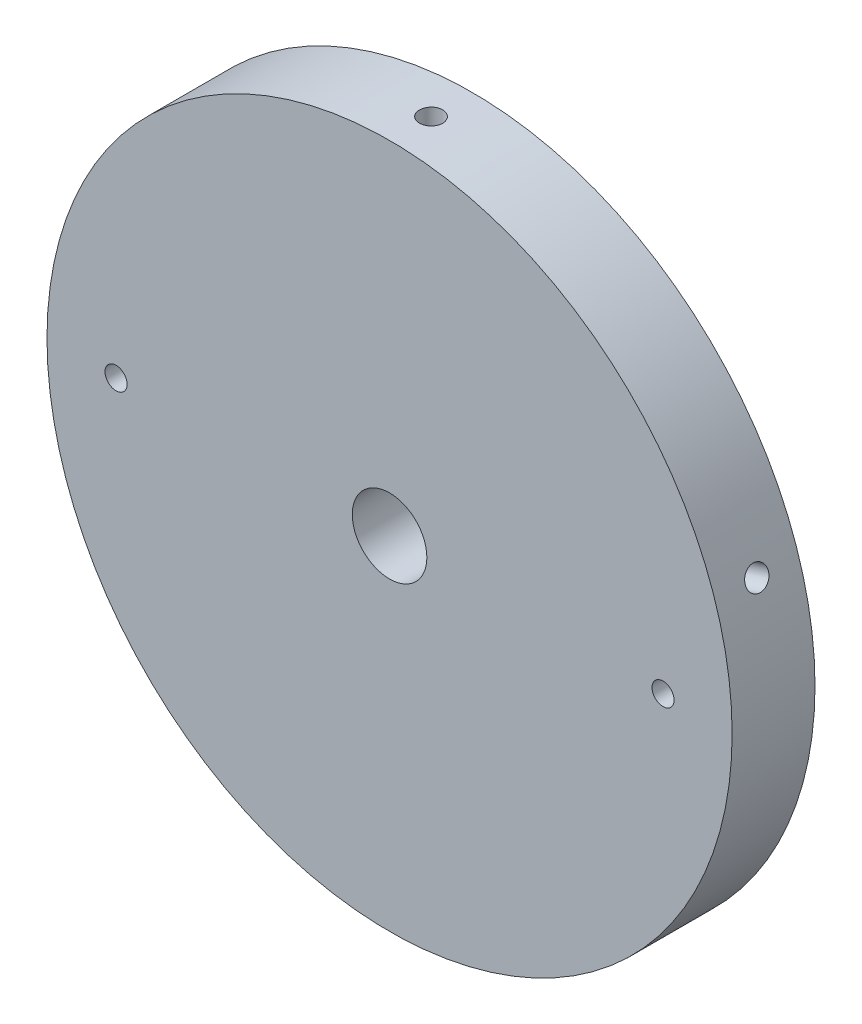
SolidWorks part; units mm, degrees
material "Polyetheretherketone (PEEK)"
ref_plane "Front Plane" through (0, 0, 0) normal (0, 0, 1) x (1, 0, 0)
ref_plane "Top Plane" through (0, 0, 0) normal (0, 1, 0) x (1, 0, 0)
ref_plane "Right Plane" through (0, 0, 0) normal (1, 0, 0) x (0, 0, -1)
sketch "Sketch1" plane through (0, 0, 0) normal (0, 0, 1) x (1, 0, 0)
  circle A0 centre (0, 0) radius 62
  dimension "D1" = 124
extrude "Boss-Extrude1" add sketch "Sketch1" along normal blind 15 contours A0
sketch "Sketch7" plane through (0, 0, 0) normal (0, 0, -1) x (-1, 0, 0)
  line L0 (0, 0) -> (-42.8683, 24.75) construction
  line L2 (0, 0) -> (-42.8683, -24.75) construction
  line L3 (-42.8683, -24.75) -> (-42.8683, 24.75) construction
  line L5 (0, 6.6) -> (0, -6.6) construction
  point P0 (-42.8683, 24.75)
  point P2 (-42.8683, -24.75)
  point P20 (42.8683, -24.75)
  point P21 (42.8683, 24.75)
  dimension "D1" = 49.5
  dimension "D2" = 49.5
sketch "Sketch9" plane through (0, 0, 0) normal (0, 0, -1) x (-1, 0, 0)
  point P0 (0, 0)
hole_wizard "M12 Clearance Hole1" positions "Sketch9" profile "Sketch10" hole size "M12" standard "ISO" end condition up to next
sketch "Sketch10" plane through (0, 0, 0) normal (1, 0, 0) x (0, 1, 0)
  line L0 (0, 0) -> (0, 15)
  line L1 (0, 15) -> (6.75, 15)
  line L2 (6.75, 15) -> (6.75, 0)
  line L5 (6.75, 0) -> (0, 0)
  line L11 (0, -6.35) -> (0, 107.95) construction
  dimension "Thru Hole Dia." = 13.5
  dimension "Thru Hole Depth" = 15
hole_wizard "M5 Tapped Hole1" positions "3DSketch1" profile "Sketch11" tap size "M5" standard "ISO"
sketch3d "3DSketch1"
  line L1 (0, 62, 7.5) -> (-58.9655, 19.1591, 7.5) construction
  line L2 (-58.9655, 19.1591, 7.5) -> (-36.4427, -50.1591, 7.5) construction
  line L3 (-36.4427, -50.1591, 7.5) -> (36.4427, -50.1591, 7.5) construction
  line L4 (36.4427, -50.1591, 7.5) -> (58.9655, 19.1591, 7.5) construction
  line L5 (58.9655, 19.1591, 7.5) -> (0, 62, 7.5) construction
  circle A0 centre (0, 0, 7.5) radius 62 construction
  circle A1 centre (0, 0, 0) radius 62 construction
  point P0 (0, 62, 7.5)
  point P2 (58.9655, 19.1591, 7.5)
  point P4 (36.4427, -50.1591, 7.5)
  point P6 (-36.4427, -50.1591, 7.5)
  point P8 (-58.9655, 19.1591, 7.5)
  point P13 (0, 0, 69.5)
  point P19 (0, 0, 62)
  dimension "D1" = 7.5
sketch "Sketch11" plane through (0, 62, 7.5) normal (1, 0, 0) x (0, 0, 1)
  line L0 (0, 0) -> (0, 13.6618)
  line L1 (0, 13.6618) -> (2.1, 12.4)
  line L2 (2.1, 12.4) -> (2.1, 0)
  line L5 (2.1, 0) -> (0, 0)
  line L10 (0, 13.6618) -> (-2.1, 12.4) construction
  line L11 (0, -6.35) -> (0, 107.95) construction
  dimension "Tap Drill Dia." = 4.2
  dimension "Tap Drill Depth" = 12.4
  dimension "Drill Angle" = 118
cosmetic thread "Hole Thread1" parameters "D1"=10, "D2"=5
cosmetic thread "Hole Thread2" parameters "D1"=10, "D2"=5
cosmetic thread "Hole Thread3" parameters "D1"=10, "D2"=5
cosmetic thread "Hole Thread4" parameters "D1"=10, "D2"=5
cosmetic thread "Hole Thread5" parameters "D1"=10, "D2"=5
sketch "Sketch12" plane through (0, 0, 0) normal (0, 0, -1) x (-1, 0, 0)
  line L0 (8.25, 0) -> (-8.25, 0) construction
  line L1 (0, 8.25) -> (0, -8.25) construction
  circle A0 centre (-49.5, 0) radius 2
  circle A1 centre (49.5, 0) radius 2
  dimension "D1" = 4
  dimension "D2" = 49.5
extrude "Cut-Extrude1" cut sketch "Sketch12" against normal blind 32
